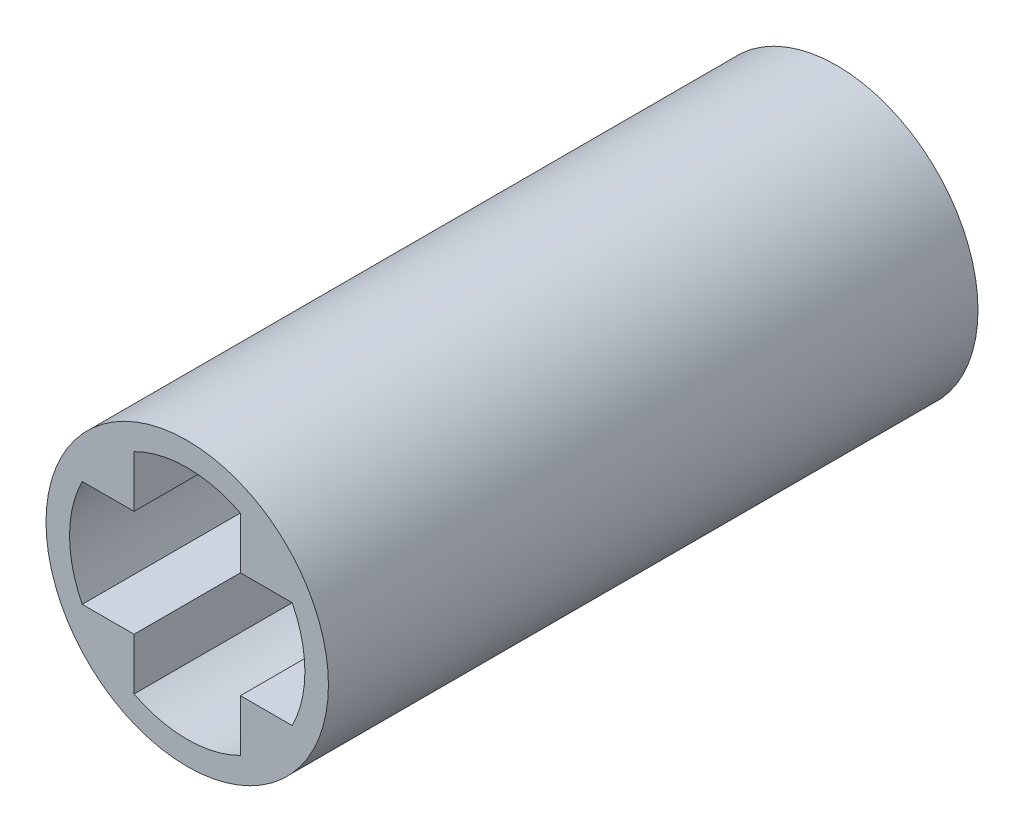
SolidWorks part; units mm, degrees
ref_plane "前视基准面" through (0, 0, 0) normal (0, 0, 1) x (1, 0, 0)
ref_plane "上视基准面" through (0, 0, 0) normal (0, 1, 0) x (1, 0, 0)
ref_plane "右视基准面" through (0, 0, 0) normal (1, 0, 0) x (0, 0, -1)
other "Configuration Table"
sketch "草图1" plane through (0, 0, 0) normal (0, 0, 1) x (1, 0, 0)
  line L0 (0, 0) -> (1.5767, 0.7593) construction
  line L1 (0, 0) -> (1.4739, 0.7292)
  line L2 (0, 0) -> (1.4739, -0.7292)
  line L3 (0, 0) -> (1.5767, -0.7593) construction
  line L4 (0, 0) -> (2.6875, 0) construction
  line L5 (1.5767, 0.7593) -> (1.5767, -0.7593) construction
  circle A0 centre (0, 0) radius 1.5625
  circle A1 centre (0, 0) radius 2.6875
  circle A2 centre (0, 0) radius 1.6445 construction
  circle A3 centre (0, 0) radius 1.75 construction
  circle A4 centre (0, 0) radius 3
  spline S0 degree 4 poles (1.4739, 0.7292) (1.4852, 0.7348) (1.5177, 0.7479) (1.5833, 0.763) (1.6919, 0.7727) (1.8331, 0.7633) (2.0108, 0.7257) (2.2103, 0.6508) (2.4152, 0.538) (2.6172, 0.3871) (2.7989, 0.2125) (2.9596, 0.0185) (3.106, -0.2014) (3.2579, -0.4913) (3.3938, -0.8578) (3.4873, -1.3025) (3.5144, -1.8062) (3.4677, -2.3088) (3.3554, -2.7995) (3.1786, -3.2732) (2.9504, -3.7195) (2.6644, -4.1402) (2.3463, -4.5197) (1.9672, -4.8748) (1.6593, -5.1166) (1.2896, -5.3555) (1.0701, -5.477) (0.8154, -5.6085) (0.6822, -5.6618) (0.5668, -5.7134) (0.5306, -5.726) (0.5053, -5.7363) (0.4917, -5.742) knots 0 0 0 0 0 0.005604 0.015718 0.02996 0.048734 0.068727 0.096889 0.125051 0.153212 0.181374 0.209535 0.237696 0.271429 0.327752 0.384075 0.440398 0.496721 0.553044 0.609367 0.66569 0.722013 0.778336 0.834659 0.890982 0.909091 0.954545 0.977273 0.988636 0.994318 1 1 1 1 1 construction
  spline S1 degree 4 poles (1.4739, 0.7292) (1.4852, 0.7348) (1.5177, 0.7479) (1.5833, 0.763) (1.6919, 0.7727) (1.8331, 0.7633) (2.0108, 0.7257) (2.2103, 0.6508) (2.4152, 0.538) (2.6172, 0.3871) (2.7989, 0.2125) (2.9596, 0.0185) (3.106, -0.2014) (3.2579, -0.4913) (3.3938, -0.8578) (3.4873, -1.3025) (3.5144, -1.8062) (3.4677, -2.3088) (3.3554, -2.7995) (3.1786, -3.2732) (2.9504, -3.7195) (2.6644, -4.1402) (2.3463, -4.5197) (1.9672, -4.8748) (1.6593, -5.1166) (1.385, -5.2938) (1.2547, -5.3715) (1.2229, -5.3899) knots 0 0 0 0 0 0.005604 0.015718 0.02996 0.048734 0.068727 0.096889 0.125051 0.153212 0.181374 0.209535 0.237696 0.271429 0.327752 0.384075 0.440398 0.496721 0.553044 0.609367 0.66569 0.722013 0.778336 0.834659 0.890982 0.909091 0.909091 0.909091 0.909091 0.909091
  spline S2 degree 4 poles (1.4739, -0.7292) (1.4852, -0.7348) (1.5177, -0.7479) (1.5833, -0.763) (1.6919, -0.7727) (1.8331, -0.7633) (2.0108, -0.7257) (2.2103, -0.6508) (2.4152, -0.538) (2.6172, -0.3871) (2.7989, -0.2125) (2.9596, -0.0185) (3.106, 0.2014) (3.2579, 0.4913) (3.3938, 0.8578) (3.4873, 1.3025) (3.5144, 1.8062) (3.4677, 2.3088) (3.3554, 2.7995) (3.1786, 3.2732) (2.9504, 3.7195) (2.6644, 4.1402) (2.3463, 4.5197) (1.9672, 4.8748) (1.6593, 5.1166) (1.2896, 5.3555) (1.0701, 5.477) (0.8154, 5.6085) (0.6822, 5.6618) (0.5668, 5.7134) (0.5306, 5.726) (0.5053, 5.7363) (0.4917, 5.742) knots 0 0 0 0 0 0.005604 0.015718 0.02996 0.048734 0.068727 0.096889 0.125051 0.153212 0.181374 0.209535 0.237696 0.271429 0.327752 0.384075 0.440398 0.496721 0.553044 0.609367 0.66569 0.722013 0.778336 0.834659 0.890982 0.909091 0.954545 0.977273 0.988636 0.994318 1 1 1 1 1 construction
  spline S3 degree 4 poles (1.4739, -0.7292) (1.4852, -0.7348) (1.5177, -0.7479) (1.5833, -0.763) (1.6919, -0.7727) (1.8331, -0.7633) (2.0108, -0.7257) (2.2103, -0.6508) (2.4152, -0.538) (2.6172, -0.3871) (2.7989, -0.2125) (2.9596, -0.0185) (3.106, 0.2014) (3.2579, 0.4913) (3.3938, 0.8578) (3.4873, 1.3025) (3.5144, 1.8062) (3.4677, 2.3088) (3.3554, 2.7995) (3.1786, 3.2732) (2.9504, 3.7195) (2.6644, 4.1402) (2.3463, 4.5197) (1.9672, 4.8748) (1.6593, 5.1166) (1.385, 5.2938) (1.2547, 5.3715) (1.2229, 5.3899) knots 0 0 0 0 0 0.005604 0.015718 0.02996 0.048734 0.068727 0.096889 0.125051 0.153212 0.181374 0.209535 0.237696 0.271429 0.327752 0.384075 0.440398 0.496721 0.553044 0.609367 0.66569 0.722013 0.778336 0.834659 0.890982 0.909091 0.909091 0.909091 0.909091 0.909091
  point P16 (1.5767, 0)
  dimension "内啮合齿顶圆直径" = 3.125
  dimension "内啮合分度圆直径" = 3.5
  dimension "内啮合基圆直径" = 3.2889
  dimension "内啮合齿根圆直径" = 5.375
  dimension "外径" = 6
  dimension "渐开线镜像线夹角" = 25.714
extrude "凸台-拉伸1" add sketch "草图1" along normal blind 5 contours A4 | A0
extrude "切除-拉伸2" cut sketch "草图1<3>" along normal through all contours A0 S3 A1 S1 region at (2.0268, 0, 0)
sketch "草图1<3>" plane through (0, 0, 0) normal (0, 0, 1) x (1, 0, 0) same geometry as "草图1"
pattern_circular "阵列(圆周)1" count 7 over 360 about axis through (0, 0, 5) along (0, 0, 1) of "切除-拉伸2"
sketch "草图2" plane through (0, 0, 5) normal (0, 0, 1) x (1, 0, 0)
  line L1 (-1.13, 2.23) -> (1.13, 2.23)
  line L2 (-1.13, 2.23) -> (-1.13, -2.23)
  line L3 (-1.13, -2.23) -> (1.13, -2.23)
  line L4 (1.13, 2.23) -> (1.13, -2.23)
  line L5 (-1.13, 2.23) -> (1.13, -2.23) construction
  line L6 (-1.13, -2.23) -> (1.13, 2.23) construction
  line L7 (-2.23, -1.13) -> (2.23, -1.13)
  line L8 (-2.23, -1.13) -> (-2.23, 1.13)
  line L9 (-2.23, 1.13) -> (2.23, 1.13)
  line L10 (2.23, -1.13) -> (2.23, 1.13)
  line L11 (-2.23, -1.13) -> (2.23, 1.13) construction
  line L12 (-2.23, 1.13) -> (2.23, -1.13) construction
  circle A0 centre (0, 0) radius 3
  circle A1 centre (0, 0) radius 3 construction
  circle A3 centre (0, 0) radius 2.5
  point P5 (0, 0)
  point P10 (0, 0)
  spline M7 degree 4 poles (0.3829, -1.5993) (0.3859, -1.6114) (0.3914, -1.6461) (0.3916, -1.7134) (0.3769, -1.8214) (0.3363, -1.957) (0.2601, -2.1219) (0.1427, -2.2997) (-0.0129, -2.4744) (-0.205, -2.6377) (-0.4156, -2.776) (-0.6405, -2.8895) (-0.8875, -2.9833) (-1.204, -3.0669) (-1.5915, -3.1178) (-2.0458, -3.1101) (-2.5429, -3.0244) (-3.0226, -2.867) (-3.476, -2.6483) (-3.8985, -2.3706) (-4.2827, -2.0488) (-4.6293, -1.6763) (-4.9285, -1.2818) (-5.1903, -0.8331) (-5.3575, -0.4792) (-5.4693, -0.1723) (-5.516, -0.0279) (-5.5269, 0.0072) knots 0 0 0 0 0 0.005604 0.015718 0.02996 0.048734 0.068727 0.096889 0.125051 0.153212 0.181374 0.209535 0.237696 0.271429 0.327752 0.384075 0.440398 0.496721 0.553044 0.609367 0.66569 0.722013 0.778336 0.834659 0.890982 0.909091 0.909091 0.909091 0.909091 0.909091 only from (0.3894, -1.7061) to (-0.2667, -2.6742)
  spline M9 degree 4 poles (4.9827, -2.3916) (4.9576, -2.4185) (4.8529, -2.5283) (4.619, -2.7563) (4.3148, -3.0026) (3.8842, -3.2932) (3.4435, -3.5189) (2.9697, -3.7041) (2.4839, -3.8273) (1.9827, -3.8943) (1.4793, -3.8946) (0.9788, -3.8282) (0.4938, -3.6897) (0.0811, -3.4996) (-0.246, -3.2856) (-0.4948, -3.073) (-0.6766, -2.8812) (-0.83, -2.6814) (-0.9597, -2.4654) (-1.062, -2.235) (-1.1263, -2.01) (-1.155, -1.7989) (-1.1521, -1.6172) (-1.1298, -1.4775) (-1.0962, -1.3738) (-1.0668, -1.3133) (-1.0468, -1.2844) (-1.0389, -1.2747) knots 0 0 0 0 0 0.018109 0.074432 0.130755 0.187078 0.243401 0.299724 0.356047 0.41237 0.468693 0.525016 0.581339 0.637662 0.671395 0.699556 0.727717 0.755879 0.78404 0.812202 0.840364 0.860357 0.879131 0.893373 0.903487 0.909091 0.909091 0.909091 0.909091 0.909091 only from (-0.9201, -2.5251) to (-1.0911, -1.3682)
  spline M15 degree 4 poles (1.2368, -5.3867) (1.2002, -5.3839) (1.0491, -5.3705) (0.725, -5.3298) (0.3427, -5.2456) (-0.1529, -5.0901) (-0.6042, -4.8862) (-1.0444, -4.6313) (-1.4436, -4.3283) (-1.8085, -3.9782) (-2.1226, -3.5848) (-2.3827, -3.1522) (-2.5769, -2.6866) (-2.6855, -2.2453) (-2.7221, -1.8562) (-2.7111, -1.5291) (-2.6745, -1.2674) (-2.6139, -1.0229) (-2.5259, -0.7868) (-2.4095, -0.5632) (-2.2737, -0.3726) (-2.1266, -0.2186) (-1.9827, -0.1076) (-1.8596, -0.0379) (-1.7575, 0.0005) (-1.6919, 0.0153) (-1.6569, 0.0176) (-1.6444, 0.0175) knots 0 0 0 0 0 0.018109 0.074432 0.130755 0.187078 0.243401 0.299724 0.356047 0.41237 0.468693 0.525016 0.581339 0.637662 0.671395 0.699556 0.727717 0.755879 0.78404 0.812202 0.840364 0.860357 0.879131 0.893373 0.903487 0.909091 0.909091 0.909091 0.909091 0.909091 only from (-2.5479, -0.855) to (-1.75, 0)
  spline M19 degree 4 poles (-1.6444, -0.0175) (-1.6569, -0.0176) (-1.6919, -0.0153) (-1.7575, -0.0005) (-1.8596, 0.0379) (-1.9827, 0.1076) (-2.1266, 0.2186) (-2.2737, 0.3726) (-2.4095, 0.5632) (-2.5259, 0.7868) (-2.6139, 1.0229) (-2.6745, 1.2674) (-2.7111, 1.5291) (-2.7221, 1.8562) (-2.6855, 2.2453) (-2.5769, 2.6866) (-2.3827, 3.1522) (-2.1226, 3.5848) (-1.8085, 3.9782) (-1.4436, 4.3283) (-1.0444, 4.6313) (-0.6042, 4.8862) (-0.1529, 5.0901) (0.3427, 5.2456) (0.725, 5.3298) (1.0491, 5.3705) (1.2002, 5.3839) (1.2368, 5.3867) knots 0 0 0 0 0 0.005604 0.015718 0.02996 0.048734 0.068727 0.096889 0.125051 0.153212 0.181374 0.209535 0.237696 0.271429 0.327752 0.384075 0.440398 0.496721 0.553044 0.609367 0.66569 0.722013 0.778336 0.834659 0.890982 0.909091 0.909091 0.909091 0.909091 0.909091 only from (-1.75, 0) to (-2.5479, 0.855)
  spline M25 degree 4 poles (-1.0389, 1.2747) (-1.0468, 1.2844) (-1.0668, 1.3133) (-1.0962, 1.3738) (-1.1298, 1.4775) (-1.1521, 1.6172) (-1.155, 1.7989) (-1.1263, 2.01) (-1.062, 2.235) (-0.9597, 2.4654) (-0.83, 2.6814) (-0.6766, 2.8812) (-0.4948, 3.073) (-0.246, 3.2856) (0.0811, 3.4996) (0.4938, 3.6897) (0.9788, 3.8282) (1.4793, 3.8946) (1.9827, 3.8943) (2.4839, 3.8273) (2.9697, 3.7041) (3.4435, 3.5189) (3.8842, 3.2932) (4.3148, 3.0026) (4.619, 2.7563) (4.8529, 2.5283) (4.9576, 2.4185) (4.9827, 2.3916) knots 0 0 0 0 0 0.005604 0.015718 0.02996 0.048734 0.068727 0.096889 0.125051 0.153212 0.181374 0.209535 0.237696 0.271429 0.327752 0.384075 0.440398 0.496721 0.553044 0.609367 0.66569 0.722013 0.778336 0.834659 0.890982 0.909091 0.909091 0.909091 0.909091 0.909091 only from (-1.0911, 1.3682) to (-0.9201, 2.5251)
  spline M27 degree 4 poles (-5.5269, -0.0072) (-5.516, 0.0279) (-5.4693, 0.1723) (-5.3575, 0.4792) (-5.1903, 0.8331) (-4.9285, 1.2818) (-4.6293, 1.6763) (-4.2827, 2.0488) (-3.8985, 2.3706) (-3.476, 2.6483) (-3.0226, 2.867) (-2.5429, 3.0244) (-2.0458, 3.1101) (-1.5915, 3.1178) (-1.204, 3.0669) (-0.8875, 2.9833) (-0.6405, 2.8895) (-0.4156, 2.776) (-0.205, 2.6377) (-0.0129, 2.4744) (0.1427, 2.2997) (0.2601, 2.1219) (0.3363, 1.957) (0.3769, 1.8214) (0.3916, 1.7134) (0.3914, 1.6461) (0.3859, 1.6114) (0.3829, 1.5993) knots 0 0 0 0 0 0.018109 0.074432 0.130755 0.187078 0.243401 0.299724 0.356047 0.41237 0.468693 0.525016 0.581339 0.637662 0.671395 0.699556 0.727717 0.755879 0.78404 0.812202 0.840364 0.860357 0.879131 0.893373 0.903487 0.909091 0.909091 0.909091 0.909091 0.909091 only from (-0.2667, 2.6742) to (0.3894, 1.7061)
  spline M37 degree 4 poles (1.4739, 0.7292) (1.4852, 0.7348) (1.5177, 0.7479) (1.5833, 0.763) (1.6919, 0.7727) (1.8331, 0.7633) (2.0108, 0.7257) (2.2103, 0.6508) (2.4152, 0.538) (2.6172, 0.3871) (2.7989, 0.2125) (2.9596, 0.0185) (3.106, -0.2014) (3.2579, -0.4913) (3.3938, -0.8578) (3.4873, -1.3025) (3.5144, -1.8062) (3.4677, -2.3088) (3.3554, -2.7995) (3.1786, -3.2732) (2.9504, -3.7195) (2.6644, -4.1402) (2.3463, -4.5197) (1.9672, -4.8748) (1.6593, -5.1166) (1.385, -5.2938) (1.2547, -5.3715) (1.2229, -5.3899) knots 0 0 0 0 0 0.005604 0.015718 0.02996 0.048734 0.068727 0.096889 0.125051 0.153212 0.181374 0.209535 0.237696 0.271429 0.327752 0.384075 0.440398 0.496721 0.553044 0.609367 0.66569 0.722013 0.778336 0.834659 0.890982 0.909091 0.909091 0.909091 0.909091 0.909091 only from (1.5767, 0.7593) to (2.6665, 0.3351)
  spline M39 degree 4 poles (1.2229, 5.3899) (1.2547, 5.3715) (1.385, 5.2938) (1.6593, 5.1166) (1.9672, 4.8748) (2.3463, 4.5197) (2.6644, 4.1402) (2.9504, 3.7195) (3.1786, 3.2732) (3.3554, 2.7995) (3.4677, 2.3088) (3.5144, 1.8062) (3.4873, 1.3025) (3.3938, 0.8578) (3.2579, 0.4913) (3.106, 0.2014) (2.9596, -0.0185) (2.7989, -0.2125) (2.6172, -0.3871) (2.4152, -0.538) (2.2103, -0.6508) (2.0108, -0.7257) (1.8331, -0.7633) (1.6919, -0.7727) (1.5833, -0.763) (1.5177, -0.7479) (1.4852, -0.7348) (1.4739, -0.7292) knots 0 0 0 0 0 0.018109 0.074432 0.130755 0.187078 0.243401 0.299724 0.356047 0.41237 0.468693 0.525016 0.581339 0.637662 0.671395 0.699556 0.727717 0.755879 0.78404 0.812202 0.840364 0.860357 0.879131 0.893373 0.903487 0.909091 0.909091 0.909091 0.909091 0.909091 only from (2.6665, -0.3351) to (1.5767, -0.7593)
  dimension "D1" = 5
  dimension "D2" = 1.1
extrude "凸台-拉伸2" add sketch "草图2" along normal blind 8.8 contours A0
extrude "切除-拉伸3" cut sketch "草图2<4>" against normal offset from surface (7.8 mm away) 1 from surface contours L1 A3 M27 | A3 L1 M27 M25 | A3 L1 M25 | A3 L8 M19 M15 | L8 A3 M19 | A3 L8 M15 | A3 L3 M7 | A3 L3 M9 M7 | L3 A3 M9 | A3 L10 M37 | A3 L10 M39 M37 | L10 A3 M39 | L2 L3 L4 L1 | L7 L10 L9 L8 region at (0, 2.3385, 5) region at (-2.3385, 0, 5) region at (2.3385, 0, 5) region at (0, -2.3385, 5) up to face at (0, 0, 5) starting at face at (3, 0, 13.8)
sketch "草图2<4>" plane through (0, 0, 5) normal (0, 0, 1) x (1, 0, 0) same geometry as "草图2"
equation "\"m\"= 0.5'模数"
equation "\"z1\"= 7'外啮合齿轮数"
equation "\"a\"= 20度'压力角"
equation "\"z2\"= 7'内啮合齿轮数"
equation "\"hax\"= 1'齿顶高系数"
equation "\"cx\"= 0.25'顶隙系数"
equation "\"ha\"= \"hax\" * \"m\"'齿顶高"
equation "\"hf\"= ( \"hax\" + \"cx\" ) * \"m\"'齿根高"
equation "\"d1\"= \"m\" * \"z1\"'外啮合分度圆直径"
equation "\"da1\"= ( \"z1\" + 2 ) * \"m\"'外啮合齿顶圆直径"
equation "\"df1\"= \"d1\" - 2 * \"hf\"'外啮合齿根圆直径"
equation "\"db1\"= \"d1\" * cos ( \"a\" )'外啮合基圆直径"
equation "\"p\"= \"m\" * PI'齿距"
equation "\"d2\"= \"m\" * \"z2\"'内啮合分度圆直径"
equation "\"db2\"= \"d2\" * cos ( \"a\" )'内啮合基圆直径"
equation "\"da2\"= ( \"z2\" - 2 ) * \"m\"'内啮合齿顶圆直径"
equation "\"df2\"= \"d2\" + 2 * \"hf\"'内啮合齿根圆直径"
equation "\"内啮合齿顶圆直径@草图1\" = \"da2\" + 1 * \"hf\""
equation "\"内啮合齿根圆直径@草图1\" = \"df2\" + 1 * \"hf\""
equation "\"内啮合分度圆直径@草图1\"= \"d2\""
equation "\"内啮合基圆直径@草图1\"= \"db2\""
equation "\"渐开线镜像线夹角@草图1\"= 360度 / 4 / \"z2\" + 360度 / 4 / \"z2\""
equation "\"do\"= IIF ( \"edo\" >= ( \"df2\" + 1 ) , \"edo\" , ( \"df2\" + 1 ) )'外圈直径"
equation "\"h\"= 5'厚度"
equation "\"外径@草图1\"= \"do\""
equation "\"厚度@凸台-拉伸1\"= \"h\""
equation "\"内啮合齿轮数@阵列(圆周)1\"= \"z2\""
equation "\"edo\"= 6'期望的外圈直径"
